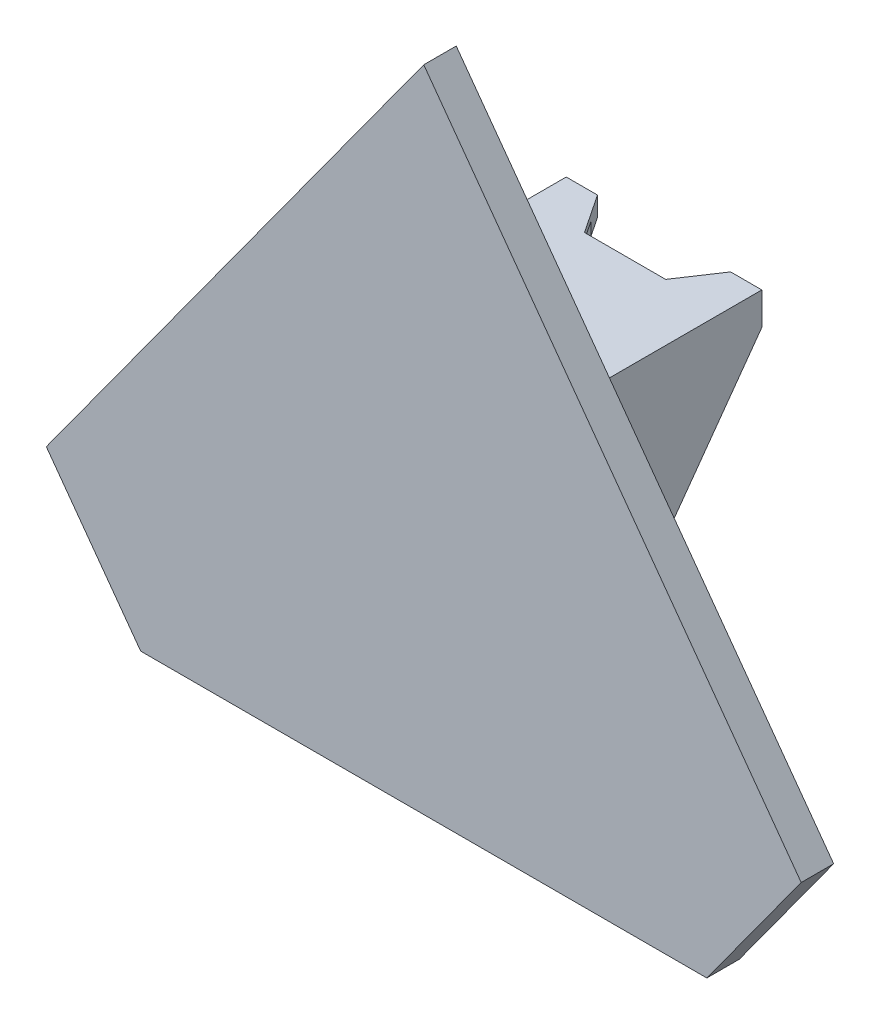
SolidWorks part; units mm, degrees
ref_plane "Front Plane" through (0, 0, 0) normal (0, 0, 1) x (1, 0, 0)
ref_plane "Top Plane" through (0, 0, 0) normal (0, 1, 0) x (1, 0, 0)
ref_plane "Right Plane" through (0, 0, 0) normal (1, 0, 0) x (0, 0, -1)
sketch "Sketch2" plane through (0, 0, 0) normal (0, 1, 0) x (1, 0, 0)
  line L0 (15.061, 0) -> (15.061, 32)
  line L1 (-12.561, 2.5) -> (12.561, 2.5)
  line L2 (-12.561, 2.5) -> (-12.561, 32)
  line L4 (12.561, 2.5) -> (12.561, 32)
  line L5 (15.061, 32) -> (12.561, 32)
  line L7 (-15.061, 32) -> (-15.061, 0)
  line L8 (-15.061, 0) -> (15.061, 0)
  line L10 (-15.061, 32) -> (-12.561, 32)
  point P4 (0, 2.5)
  point P12 (0, 0)
  dimension "D1" = 2.5
  dimension "D2" = 2.5
  dimension "D3" = 29.5
  dimension "D4" = 25.122
extrude "Boss-Extrude1" add sketch "Sketch2" along normal blind 32.5
sketch "Sketch4" plane through (0, 0, 0) normal (0, -1, 0) x (1, 0, 0)
  line L4 (-7.5, -6) -> (7.5, -6)
  line L9 (15.061, 0) -> (-15.061, 0)
  line L13 (-12.561, -2.5) -> (-12.561, -32) construction
  line L18 (-12.561, -10) -> (-7.5, -6)
  line L23 (12.561, -32) -> (12.561, -2.5) construction
  line L26 (12.561, -10) -> (7.5, -6)
  line L32 (-12.561, -10) -> (-15.061, -10)
  line L33 (-15.061, -32) -> (-15.061, 0) construction
  line L34 (-15.061, -10) -> (-15.061, 0)
  line L35 (12.561, -10) -> (15.061, -10)
  line L36 (15.061, 0) -> (15.061, -32) construction
  line L37 (15.061, -10) -> (15.061, 0)
  circle A2 centre (-10.2499, -4.95) radius 1.05
  circle A5 centre (10.2499, -4.95) radius 1.05
  point P31 (0, -6)
  dimension "D5" = 2.1
  dimension "D10" = 15
  dimension "D11" = 10
  dimension "D2" = 6
  dimension "D7" = 4.95
extrude "Boss-Extrude2" add sketch "Sketch4" along normal blind 2.5
sketch "Sketch5" plane through (0, 32.5, 0) normal (0, 1, 0) x (1, 0, 0)
  line L0 (-15.061, 32) -> (-10.2499, 32)
  line L9 (-10.2499, 32) -> (-6.25, 26)
  line L13 (-15.061, 0) -> (15.061, 0) construction
  line L14 (15.061, 0) -> (-15.061, 0)
  line L15 (-15.061, 0) -> (-15.061, 32)
  line L20 (15.061, 0) -> (15.061, 32)
  line L21 (-6.25, 26) -> (6.25, 26)
  line L22 (6.25, 26) -> (10.2499, 32)
  line L23 (10.2499, 32) -> (15.061, 32)
  circle A0 centre (-10.2499, 4.95) radius 1.05 construction
  circle A1 centre (-10.2499, 8.7) radius 1.05
  circle A2 centre (10.2499, 8.7) radius 1.05
  point P6 (0, 26)
  dimension "D4" = 0
  dimension "D1" = 8.7
  dimension "D2" = 12.5
  dimension "D3" = 20.4998
  dimension "D5" = 6
extrude "Boss-Extrude3" add sketch "Sketch5" along normal blind 3
sketch "Sketch6" plane through (-15.061, 0, 0) normal (-1, 0, 0) x (0, 0, 1)
  line L0 (-10, 0) -> (-32, 30.5)
  line L1 (-32, 30.5) -> (-32, 0)
  line L2 (-32, 0) -> (-10, 0)
  line L3 (-32, 35.5) -> (-32, 0) construction
  dimension "D1" = 5
extrude "Cut-Extrude1" cut sketch "Sketch6" against normal through all
ref_plane "Plane1" through (0, 16.5, 0) normal (0, -1, 0) x (-1, 0, 0)
sketch "Sketch8" plane through (0, 0, 0) normal (0, 0, 1) x (1, 0, 0)
  line L0 (0, 76.5) -> (43.5926, 16.5)
  line L1 (-16.5671, 16.5) -> (16.5671, 16.5) construction
  line L2 (43.5926, 16.5) -> (-43.5926, 16.5)
  line L3 (-43.5926, 16.5) -> (0, 76.5)
  dimension "D1" = 72
  dimension "D2" = 60
extrude "Boss-Extrude4" add sketch "Sketch8" along normal blind 5
sketch "Sketch9" plane through (0, 0, 0) normal (0, 0, 1) x (1, 0, 0)
  line L0 (-43.5926, 16.5) -> (-72.6543, -23.5)
  line L1 (-72.6543, -23.5) -> (72.6543, -23.5)
  line L2 (72.6543, -23.5) -> (43.5926, 16.5)
  line L3 (-43.5926, 16.5) -> (43.5926, 16.5)
  line L4 (0, 76.5) -> (-43.5926, 16.5) construction
  line L5 (43.5926, 16.5) -> (0, 76.5) construction
  dimension "D1" = 40
extrude "Boss-Extrude6" add sketch "Sketch9" along normal up to surface (5 mm away) up to face at (0, 36.5, 5)
sketch "Sketch10" plane through (0, 0, 0) normal (0, 0, -1) x (-1, 0, 0)
  line L0 (-43.5926, -23.5) -> (-58.1234, -3.5)
  line L1 (72.6543, -23.5) -> (-72.6543, -23.5) construction
  line L2 (-72.6543, -23.5) -> (0, 76.5) construction
  line L3 (-58.1234, -3.5) -> (-72.6543, -23.5)
  line L4 (-72.6543, -23.5) -> (-43.5926, -23.5)
  line L5 (72.6543, -23.5) -> (58.1234, -3.5)
  line L13 (0, 76.5) -> (72.6543, -23.5) construction
  line L14 (58.1234, -3.5) -> (43.5926, -23.5)
  line L15 (72.6543, -23.5) -> (-72.6543, -23.5) construction
  line L16 (43.5926, -23.5) -> (72.6543, -23.5)
  point P13 (58.1234, -23.5)
  dimension "D1" = 20
extrude "Cut-Extrude2" cut sketch "Sketch10" against normal through all
sketch "Sketch12" plane through (0, 0, -26) normal (0, 0, -1) x (-1, 0, 0)
  line L1 (-8.2499, 34.5) -> (8.2499, 34.5)
  line L2 (-8.2499, 34.5) -> (-8.2499, 32.5)
  line L3 (-8.2499, 32.5) -> (8.2499, 32.5)
  line L4 (8.2499, 34.5) -> (8.2499, 32.5)
  line L5 (6.25, 32.5) -> (10.2499, 32.5) construction
  line L6 (-10.2499, 35.5) -> (-6.25, 35.5) construction
  point P8 (-8.2499, 35.5)
  dimension "D1" = 2
extrude "Cut-Extrude4" cut sketch "Sketch12" against normal up to surface (23.5 mm away) and the other way blind 10 up to face at (0, 16.25, -2.5)
